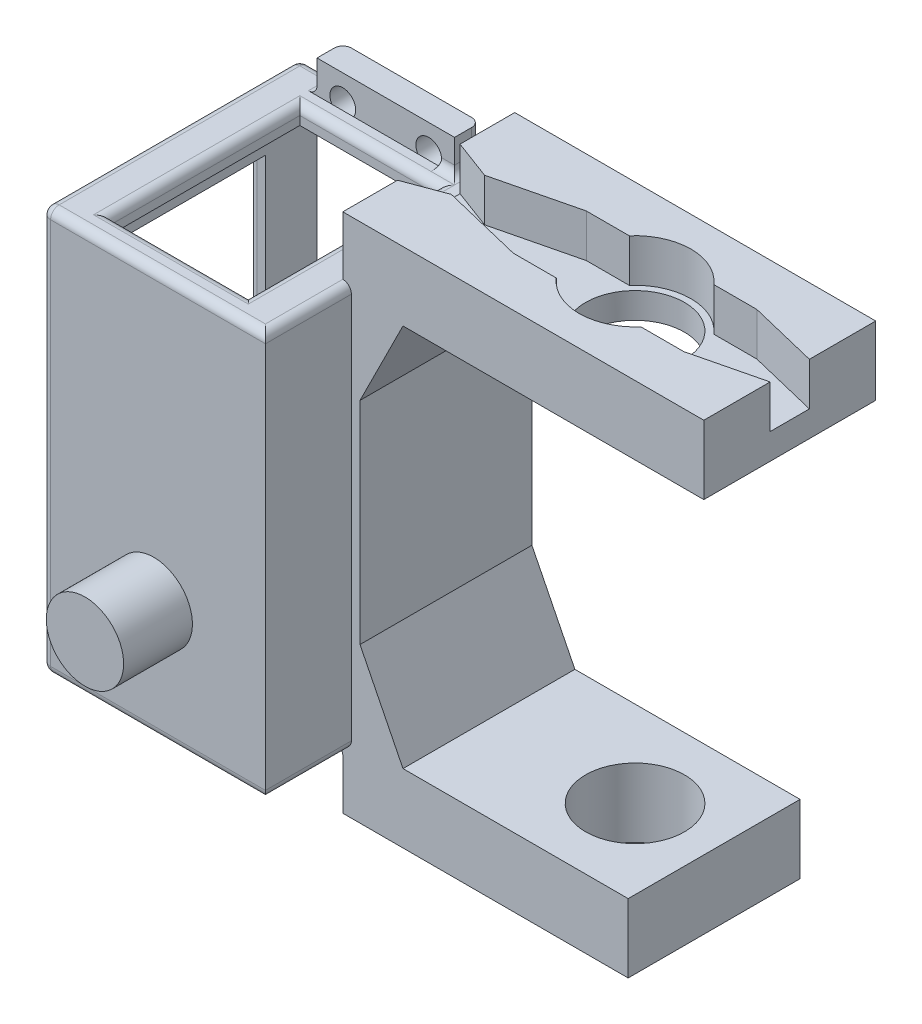
SolidWorks part; units mm, degrees
ref_plane "Front Plane" through (0, 0, 0) normal (0, 0, 1) x (1, 0, 0)
ref_plane "Top Plane" through (0, 0, 0) normal (0, 1, 0) x (1, 0, 0)
ref_plane "Right Plane" through (0, 0, 0) normal (1, 0, 0) x (0, 0, -1)
sketch "Sketch1" plane through (0, 0, 0) normal (0, 0, 1) x (1, 0, 0)
  line L1 (-13, 23.5) -> (13, 23.5)
  line L2 (-13, 23.5) -> (-13, -23.5)
  line L3 (-13, -23.5) -> (13, -23.5)
  line L4 (13, 23.5) -> (13, -23.5)
  line L5 (-13, 23.5) -> (13, -23.5) construction
  line L6 (-13, -23.5) -> (13, 23.5) construction
  point P0 (0, 0)
  dimension "D1" = 47
  dimension "D2" = 26
extrude "Boss-Extrude1" add sketch "Sketch1" along normal blind 30 contours L2 L1 L4 L3
shell "Shell1" thickness 2
sketch "Sketch2" plane through (0, 0, 30) normal (0, 0, 1) x (1, 0, 0)
  line L1 (-5, 24.3) -> (5, 24.3)
  line L2 (-5, 24.3) -> (-5, -24.3)
  line L3 (-5, -24.3) -> (5, -24.3)
  line L4 (5, 24.3) -> (5, -24.3)
  line L5 (-5, 24.3) -> (5, -24.3) construction
  line L6 (-5, -24.3) -> (5, 24.3) construction
  line L10 (-8, 27.3) -> (-8, -27.3)
  line L11 (-13, 23.5) -> (13, 23.5)
  line L12 (-13, 23.5) -> (-13, -23.5)
  line L13 (-13, -23.5) -> (13, -23.5)
  line L14 (13, 23.5) -> (13, -23.5)
  line L15 (-8, -27.3) -> (8, -27.3)
  line L16 (8, 27.3) -> (8, -27.3)
  line L17 (-8, 27.3) -> (8, 27.3)
  point P0 (0, 0)
  line M3 (-13, -23.5) -> (13, -23.5)
  line M5 (13, 23.5) -> (-13, 23.5)
  dimension "D1" = 10
  dimension "D2" = 48.6
  dimension "D3" = 3
extrude "Boss-Extrude2" add sketch "Sketch2" against normal blind 3 contours L17 L10 L2 L1 L4 L11 L16 M5 | L4 L1 L2 M5 | L16 L4 L3 L2 L10 L15 M3 | L4 L2 L3 M3
sketch "Sketch3" plane through (0, 0, 30) normal (0, 0, 1) x (1, 0, 0)
  line L1 (-5, 24.3) -> (5, 24.3) construction
  line L2 (-5, 24.3) -> (-5, -24.3) construction
  line L3 (-5, -24.3) -> (5, -24.3) construction
  line L4 (5, 24.3) -> (5, -24.3) construction
  line L5 (-5, 24.3) -> (5, -24.3) construction
  line L6 (-5, -24.3) -> (5, 24.3) construction
  circle A0 centre (-5, -24.3) radius 1.5
  circle A1 centre (5, -24.3) radius 1.5
  circle A2 centre (5, 24.3) radius 1.5
  circle A3 centre (-5, 24.3) radius 1.5
  point P0 (0, 0)
  dimension "D3" = 3
  dimension "D1" = 48.6
  dimension "D2" = 10
extrude "Cut-Extrude1" cut sketch "Sketch3" against normal blind 3
sketch "Sketch4" plane through (0, 0, 30) normal (0, 0, 1) x (1, 0, 0)
  line L0 (14, 0) -> (24, 0) construction
  line L1 (-24, 22.3) -> (24, 22.3)
  line L2 (-24, 22.3) -> (-24, -22.3)
  line L3 (-24, -22.3) -> (24, -22.3)
  line L4 (24, 22.3) -> (24, -22.3)
  line L5 (-24, 22.3) -> (24, -22.3) construction
  line L6 (-24, -22.3) -> (24, 22.3) construction
  line L7 (24, -22.3) -> (14, -22.3)
  line L8 (24, -22.3) -> (24, 22.3)
  line L9 (24, 22.3) -> (14, 22.3)
  line L10 (14, -22.3) -> (14, 22.3)
  line L11 (0, 0) -> (13, 0)
  line L12 (0, 0) -> (0, 23.5)
  line L13 (0, 23.5) -> (13, 23.5)
  line L14 (13, 0) -> (13, 23.5)
  line L15 (12, 22.3) -> (54, 22.3)
  line L16 (12, 22.3) -> (12, 30.3)
  line L17 (12, 30.3) -> (54, 30.3)
  line L18 (54, 22.3) -> (54, 30.3)
  line L19 (14, 12.3) -> (19, 22.3)
  line L20 (14, -12.3) -> (19, -22.3)
  line L21 (12, -30.3) -> (54, -30.3)
  line L22 (54, -22.3) -> (54, -30.3)
  line L23 (12, -22.3) -> (54, -22.3)
  line L24 (12, -22.3) -> (12, -30.3)
  point P0 (0, 0)
  point P8 (19, 22.3)
  point P20 (14, 12.3)
  line M10 (13, -23.5) -> (13, 23.5)
  dimension "D1" = 48
  dimension "D2" = 44.6
  dimension "D3" = 10
  dimension "D4" = 5
  dimension "D5" = 8
  dimension "D6" = 42
  dimension "D7" = 10
extrude "Boss-Extrude3" add sketch "Sketch4" against normal blind 20 contours L15 L18 L17 L16 L1 M10 | L10 L19 L1 | L3 L10 L1 M10 | L20 L10 L3 | L24 L21 L22 L23 L7 L3 M10
sketch "Sketch5" plane through (0, 22.3, 0) normal (0, -1, 0) x (-1, 0, 0)
  line L0 (-36, -30) -> (-36, -10)
  line L1 (-19, -10) -> (-54, -10)
  line L2 (-19, -10) -> (-19, -30)
  line L3 (-19, -30) -> (-54, -30)
  line L4 (-54, -10) -> (-54, -30)
  circle A0 centre (-36, -20) radius 5.75
  dimension "D2" = 11.5
  dimension "D1" = 17
extrude "Cut-Extrude2" cut sketch "Sketch5" against normal through all both and the other way through all contours L0 A0 | L0 A0
sketch "Sketch6" plane through (0, 0, 0) normal (0, 0, -1) x (-1, 0, 0)
  line L1 (-13, 23.5) -> (13, 23.5)
  line L2 (-13, 23.5) -> (-13, -23.5)
  line L3 (-13, -23.5) -> (13, -23.5)
  line L4 (13, 23.5) -> (13, -23.5)
  circle A0 centre (0, 0) radius 4.5
  circle A1 centre (0, -10) radius 4.5
  dimension "D1" = 9
  dimension "D2" = 2
extrude "Boss-Extrude4" add sketch "Sketch6" along normal blind 8 contours A1
sketch "Sketch7" plane through (0, 23.5, 0) normal (0, 1, 0) x (1, 0, 0)
  line L0 (8, -25) -> (8, -5)
  line L1 (13, -30) -> (-13, -30)
  line L2 (13, -30) -> (13, 0)
  line L3 (13, 0) -> (-13, 0)
  line L4 (-13, -30) -> (-13, 0)
  line L5 (8, -5) -> (-8, -5) construction
  line L6 (-8, -25) -> (-8, -5)
  line L7 (8, -25) -> (-8, -25)
  line L8 (8, -23) -> (8, -3)
  line L9 (8, -3) -> (-8, -3)
  line L10 (-8, -23) -> (-8, -3)
  line L11 (8, -23) -> (-8, -23) construction
  point P10 (13, 0)
  dimension "3" = 3
  dimension "D1" = 5
  dimension "D2" = 2
extrude "Cut-Extrude3" cut sketch "Sketch7" against normal through all both and the other way through all contours L10 L6 L7 L0 L8 L9
sketch "Sketch9" plane through (0, 30.3, 0) normal (0, 1, 0) x (1, 0, 0)
  line L0 (31.0819, -24.25) -> (31.0819, -15.75)
  line L1 (-30, 10) -> (54, 10)
  line L2 (-30, 10) -> (-30, -30)
  line L3 (-30, -30) -> (54, -30)
  line L4 (54, 10) -> (54, -30)
  line L5 (-30, 10) -> (54, -30) construction
  line L6 (-30, -30) -> (54, 10) construction
  line L7 (36, -20) -> (29.5, -20) construction
  line L8 (31.0819, -15.75) -> (26.0819, -15.75)
  line L9 (31.0819, -24.25) -> (26.0819, -24.25)
  line L10 (26.0819, -15.75) -> (16.5595, -18.066)
  line L11 (26.0819, -24.25) -> (16.5595, -21.934)
  line L12 (16.5595, -18.066) -> (10.3634, -15.75)
  line L13 (10.3634, -15.75) -> (10.3634, -22.7485)
  line L14 (10.3634, -22.7485) -> (10.3634, -24.25)
  line L15 (10.3634, -24.25) -> (16.5595, -21.934)
  line L16 (36, -20) -> (36, -13.5) construction
  line L17 (61.6366, -22.7485) -> (61.6366, -24.25)
  line L18 (61.6366, -15.75) -> (61.6366, -22.7485)
  line L19 (55.4405, -18.066) -> (61.6366, -15.75)
  line L20 (45.9181, -15.75) -> (55.4405, -18.066)
  line L21 (40.9181, -15.75) -> (45.9181, -15.75)
  line L22 (40.9181, -24.25) -> (40.9181, -15.75)
  line L23 (40.9181, -24.25) -> (45.9181, -24.25)
  line L24 (45.9181, -24.25) -> (55.4405, -21.934)
  line L25 (61.6366, -24.25) -> (55.4405, -21.934)
  circle A0 centre (36, -20) radius 6.5
  circle A1 centre (26.0819, -15.75) radius 9.8 construction
  point P0 (12, -10)
  dimension "D1" = 13
  dimension "D5" = 19.6
  dimension "D2" = 8.5
  dimension "D3" = 5
  dimension "D4" = 166.33
extrude "Cut-Extrude4" cut sketch "Sketch9" against normal blind 5
sketch "Sketch10" plane through (-13, 0, 0) normal (-1, 0, 0) x (0, 0, 1)
  line L0 (6, 17.5) -> (6, -17.5)
  line L1 (0, 23.5) -> (30, 23.5)
  line L2 (0, 23.5) -> (0, -23.5)
  line L3 (0, -23.5) -> (30, -23.5)
  line L4 (30, 23.5) -> (30, -23.5)
  line L5 (6, -17.5) -> (24, -17.5)
  line L6 (24, 17.5) -> (24, -17.5)
  line L7 (6, 17.5) -> (24, 17.5)
  dimension "D1" = 6
extrude "Cut-Extrude5" cut sketch "Sketch10" against normal blind 5 contours L0 L5 L6 L7
fillet "Fillet1" radius 1 5 edges at (0, -21.5, 30) (-13, 0, 6) (-13, -17.5, 15) (-13, 0, 24) (-13, 17.5, 15)
fillet "Fillet2" radius 1 3 edges at (8, 23.5, 28.5) (-8, 23.5, 28.5) (12, -23.5, 20)
fillet "Fillet3" radius 1 2 edges at (-8, -23.5, 28.5) (8, -23.5, 28.5)
fillet "Fillet5" radius 1 22 edges at (-8, 25.9, 30) (-8.2929, 23.7929, 30) (-13, 23.5, 15) (-13, 0, 0) (13, 23.5, 5) (-11, 23.5, 30) (-13, -23.5, 15) (0, -23.5, 0) (13, -23.5, 5) (-13, 0, 30) (0, 23.5, 0) (10.5, 23.5, 30) (8, 25.9, 30) (0, -23.5, 25) (-8, -23.5, 14) (0, -23.5, 3) (8, -23.5, 14) (-8, 23.5, 14) (0, 23.5, 25) (8, 23.5, 14) (0, 23.5, 3) (8.2929, 23.7929, 30)
fillet "Fillet6" radius 1 1 edges at (0, 21.5, 30)
sketch "Sketch11" plane through (0, -30.3, 0) normal (0, -1, 0) x (1, 0, 0)
  line L0 (12, 10) -> (54, 10) construction
  line L1 (54, 30) -> (45.1981, 30)
  line L2 (54, 30) -> (54, 10)
  line L3 (54, 10) -> (45.1981, 10)
  line L4 (45.1981, 30) -> (45.1981, 10)
  dimension "D1" = 8.8019
extrude "Cut-Extrude6" cut sketch "Sketch11" against normal blind 10 contours L2 L1 L4 L3
mirror "Mirror2" about plane through (0, 0, 30) normal (0, 0, -1) of bodies 110
ref_plane "Plane2" through (0, 0, 30) normal (0, 0, -1) x (-1, 0, 0)
sketch "Sketch12" plane through (0, 0, 30) normal (0, 0, -1) x (-1, 0, 0)
  circle A0 centre (0, 0) radius 109.3131
extrude "Cut-Extrude7" cut sketch "Sketch12" along normal through all
